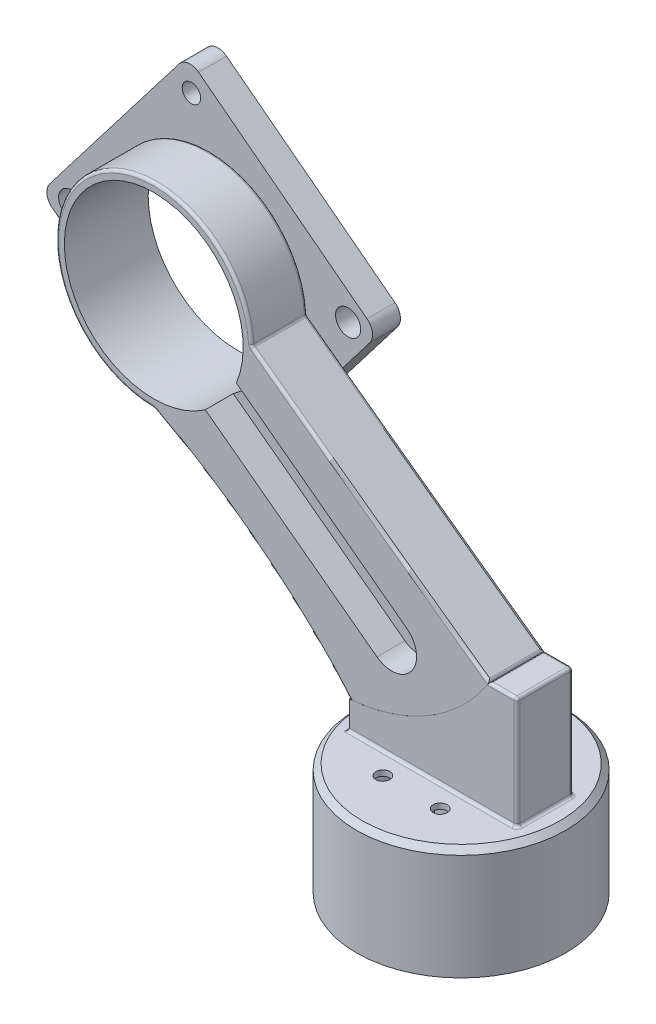
SolidWorks part; units mm, degrees
ref_plane "Front Plane" through (0, 0, 0) normal (0, 0, 1) x (1, 0, 0)
ref_plane "Top Plane" through (0, 0, 0) normal (0, 1, 0) x (1, 0, 0)
ref_plane "Right Plane" through (0, 0, 0) normal (1, 0, 0) x (0, 0, -1)
sketch "Sketch1" plane through (0, 0, 0) normal (0, 1, 0) x (1, 0, 0)
  circle A0 centre (0, 0) radius 18.73
  dimension "D1" = 37.46
extrude "Boss-Extrude1" add sketch "Sketch1" along normal blind 20
chamfer "Chamfer1" distance 1 angle 45 1 edges at (0, 20, 18.73)
sketch "Sketch2" plane through (0, 20, 0) normal (0, 1, 0) x (1, 0, 0)
  line L1 (-15, -5) -> (15, -5)
  line L2 (-15, -5) -> (-15, 5)
  line L3 (-15, 5) -> (15, 5)
  line L4 (15, -5) -> (15, 5)
  line L5 (-15, -5) -> (15, 5) construction
  line L6 (-15, 5) -> (15, -5) construction
  point P0 (0, 0)
  dimension "D1" = 30
  dimension "D2" = 10
extrude "Boss-Extrude2" add sketch "Sketch2" along normal blind 20
sketch "Sketch3" plane through (0, 0, 5) normal (0, 0, 1) x (1, 0, 0)
  line L0 (-15, 40) -> (10, 40)
  line L1 (-15, 40) -> (15, 40) construction
  line L2 (-15, 40) -> (-15, 25)
  line L3 (-15, 40) -> (-15, 20) construction
  arc A1 (-15, 25) -> (10, 40) centre (-17.5582, 57.597) ccw
  dimension "D1" = 15
  dimension "D2" = 25
extrude "Cut-Extrude1" cut sketch "Sketch3" against normal through all both and the other way through all
sketch "Sketch4" plane through (0, 0, 0) normal (0, 0, 1) x (1, 0, 0)
  line L0 (-18.73, 0) -> (18.73, 0) construction
  arc A0 (-32.5188, 70.8105) -> (-50, 52.5) centre (-50, 70) ccw
  arc A1 (-15, 25) -> (-50, 52.5) centre (-108.4938, -57.9694) ccw
  arc A2 (10, 40) -> (-32.5188, 70.8105) centre (1942.7987, 2752.0198) cw
  arc A3 (-15, 25) -> (10, 40) centre (-17.5582, 57.597) ccw construction
  arc A4 (-15, 25) -> (10, 40) centre (-17.5582, 57.597) ccw
  dimension "D3" = 35
  dimension "D1" = 50
  dimension "D2" = 70
extrude "Boss-Extrude3" add sketch "Sketch4" against normal mid plane 10 separate body
fillet "Fillet1" radius 0.5 7 edges at (-15, 20, 0) (0, 20, -5) (15, 20, 0) (0, 20, 5) (15, 30, -5) (15, 30, 5) (15, 40, 0)
fillet "Fillet2" radius 0.5 5 edges at (14.8536, 39.8536, -4.8536) (14.8536, 39.8536, 4.8536) (12.25, 40, -5) (12.25, 40, 5) (10, 40, 0)
fillet "Fillet3" radius 0.5 10 edges at (-32.5188, 70.8105, 0) (-50, 52.5, 0) (-15, 25, 0) (10, 40, 0) (-62.6577, 82.0844, 5) (-62.6577, 82.0844, -5) (-31.2661, 40.3204, 5) (-31.2661, 40.3204, -5) (-11.3201, 55.3215, 5) (-11.3201, 55.3215, -5)
sketch "Sketch8" plane through (0, 0, 5) normal (0, 0, 1) x (1, 0, 0)
  circle A0 centre (-50, 70) radius 16
  dimension "D1" = 32
extrude "Cut-Extrude2" cut sketch "Sketch8" against normal through all both and the other way through all
sketch "Sketch9" plane through (0, 0, -5) normal (0, 0, -1) x (-1, 0, 0)
  line L0 (46.0335, 39.8542) -> (80.1458, 66.0335)
  line L7 (46.0335, 39.8542) -> (19.8542, 73.9665)
  line L8 (19.8542, 73.9665) -> (53.9665, 100.1458)
  line L9 (53.9665, 100.1458) -> (80.1458, 66.0335)
  line L10 (53.9665, 100.1458) -> (46.0335, 39.8542) construction
  line L11 (19.8542, 73.9665) -> (80.1458, 66.0335) construction
  line L12 (50, 70) -> (-14.5, 20.5) construction
  circle A0 centre (50, 70) radius 16
  point P0 (50, 70)
  point P1 (0, 0)
  point P12 (50, 70)
  point P13 (101.9511, 100.8634)
  dimension "D3" = 32
  dimension "D4" = 43
extrude "Boss-Extrude6" add sketch "Sketch9" along normal blind 5
sketch "Sketch11" plane through (0, 0, -10) normal (0, 0, -1) x (-1, 0, 0)
  line L0 (46.0335, 39.8542) -> (80.1458, 66.0335) construction
  line L2 (53.9665, 100.1458) -> (46.0335, 39.8542) construction
  line L4 (19.8542, 73.9665) -> (80.1458, 66.0335) construction
  line L6 (80.1458, 66.0335) -> (53.9665, 100.1458) construction
  line L7 (53.9665, 100.1458) -> (19.8542, 73.9665) construction
  line L8 (19.8542, 73.9665) -> (46.0335, 39.8542) construction
  circle A1 centre (53.2599, 94.7756) radius 1.65
  circle A3 centre (46.7401, 45.2244) radius 1.65
  circle A6 centre (74.7756, 66.7401) radius 2.25
  circle A7 centre (25.2244, 73.2599) radius 2.25
  dimension "D2" = 3.83
  dimension "D3" = 3.3
  dimension "D4" = 3.83
  dimension "D5" = 3.83
  dimension "D6" = 3.83
  dimension "D7" = 3.3
  dimension "D8" = 3.83
  dimension "D9" = 4.5
  dimension "D10" = 4.5
  dimension "D11" = 3.83
extrude "Cut-Extrude4" cut sketch "Sketch11" against normal blind 5
sketch "Sketch12" plane through (0, 0, 5) normal (0, 0, 1) x (1, 0, 0)
  line L0 (-38.5818, 60.8222) -> (-7.4106, 37.5495) construction
  line L1 (-35.9291, 64.3752) -> (-4.7579, 41.1025)
  line L2 (-41.2345, 57.2691) -> (-10.0633, 33.9965)
  arc A0 (-35.9291, 64.3752) -> (-41.2345, 57.2691) centre (-38.5818, 60.8222) ccw
  arc A1 (-10.0633, 33.9965) -> (-4.7579, 41.1025) centre (-7.4106, 37.5495) ccw
  point P2 (-22.9962, 49.1858)
extrude "Cut-Extrude5" cut sketch "Sketch12" against normal blind 5
sketch "Sketch13" plane through (0, 0, 0) normal (0, -1, 0) x (1, 0, 0)
  line L0 (0, 18.73) -> (0, -22.7743)
  line L1 (-18.73, 0) -> (18.73, 0)
  circle A0 centre (0, 0) radius 17.73
  circle A1 centre (0, 0) radius 18.73 construction
  circle A2 centre (-5.13, 8.88) radius 1.25
  circle A3 centre (5.1253, 8.8827) radius 1.25
  circle A4 centre (10.2553, 0.0027) radius 1.25
  circle A5 centre (5.13, -8.88) radius 1.25
  circle A6 centre (-5.1253, -8.8827) radius 1.25
  circle A7 centre (-10.2553, -0.0027) radius 1.25
  point P25 (0, 0)
  dimension "D1" = 1
  dimension "D2" = 2.5
  dimension "D3" = 5.13
  dimension "D4" = 8.88
  dimension "D5" = 6
extrude "Cut-Extrude6" cut sketch "Sketch13" against normal through all contours A2 | A3 | A5 | A6 region at (-5.13, 0, 8.88) region at (5.1253, 0, 8.8827) region at (5.13, 0, -8.88) region at (-5.1253, 0, -8.8827)
sketch "Sketch15" plane through (0, 0, 0) normal (0, -1, 0) x (1, 0, 0)
  line L0 (0, 16.73) -> (0, -18.73) construction
  line L1 (-18.73, 0) -> (18.73, 0) construction
  line L2 (-1.73, 3) -> (1.73, 3)
  line L3 (-1.73, -3) -> (1.73, -3)
  line L4 (0, 0) -> (3.46, 0)
  line L5 (1.73, -3) -> (3.46, 0)
  line L6 (1.73, 3) -> (3.46, 0)
  line L7 (-1.73, -3) -> (-3.46, 0)
  line L8 (-1.73, 3) -> (-3.46, 0)
  circle A0 centre (0, 0) radius 16.73
  circle A1 centre (0, 0) radius 18.73 construction
  point P16 (0, -3)
  point P18 (0, 3)
  dimension "D1" = 2
  dimension "D2" = 1.73
  dimension "D3" = 3.46
  dimension "D4" = 1.73
  dimension "D5" = 3
  dimension "D6" = 3
extrude "Cut-Extrude8" cut sketch "Sketch15" against normal blind 19 contours A0
extrude "Boss-Extrude7" add sketch "Sketch15<5>" against normal up to next contours L2 L8 L7 L3 L5 L6 region at (0, 0, 2.9084)
sketch "Sketch15<5>" plane through (0, 0, 0) normal (0, -1, 0) x (1, 0, 0) same geometry as "Sketch15"
extrude "Boss-Extrude8" add sketch "Sketch15<7>" along normal blind 8 contours L2 L8 L7 L3 L5 L6 region at (0, 0, 2.9084)
sketch "Sketch15<7>" plane through (0, 0, 0) normal (0, -1, 0) x (1, 0, 0) same geometry as "Sketch15"
fillet "Fillet4" radius 2.5 4 edges at (-46.0335, 39.8542, -7.5) (-19.8542, 73.9665, -7.5) (-53.9665, 100.1458, -7.5) (-80.1458, 66.0335, -7.5)
